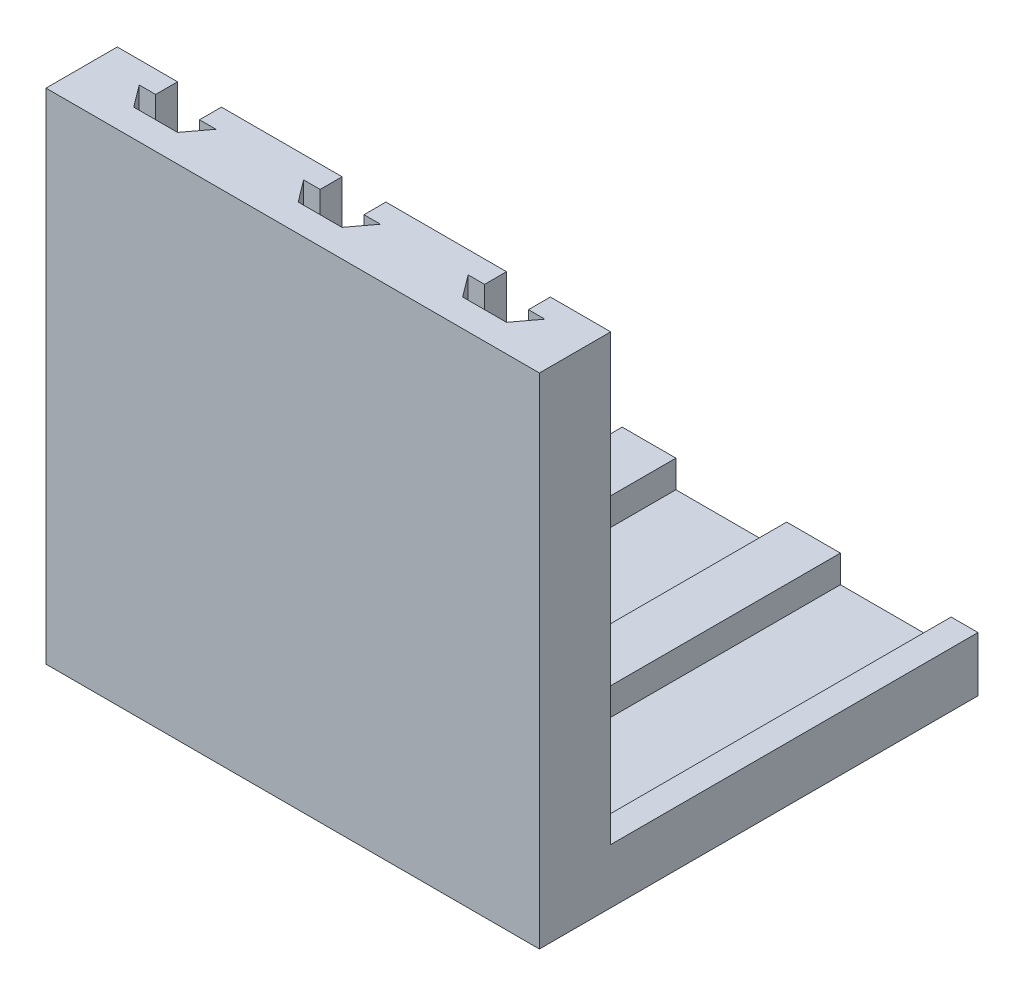
SolidWorks part; units mm, degrees
ref_plane "Front Plane" through (0, 0, 0) normal (0, 0, 1) x (1, 0, 0)
ref_plane "Top Plane" through (0, 0, 0) normal (0, 1, 0) x (1, 0, 0)
ref_plane "Right Plane" through (0, 0, 0) normal (1, 0, 0) x (0, 0, -1)
sketch "Sketch1" plane through (0, 0, 0) normal (0, 1, 0) x (1, 0, 0)
  line L1 (-15, -40) -> (15, -40)
  line L2 (-15, -40) -> (-15, 40)
  line L3 (-15, 40) -> (15, 40)
  line L4 (15, -40) -> (15, 40)
  line L5 (-15, -40) -> (15, 40) construction
  line L6 (-15, 40) -> (15, -40) construction
  point P0 (0, 0)
  dimension "D1" = 80
  dimension "D2" = 30
extrude "Boss-Extrude1" add sketch "Sketch1" along normal blind 10
sketch "Sketch2" plane through (0, 10, 0) normal (0, 1, 0) x (1, 0, 0)
  line L0 (15, -40) -> (15, 40) construction
  line L1 (-15, -40) -> (15, -40)
  line L2 (-15, -40) -> (-15, -27)
  line L3 (-15, -27) -> (15, -27)
  line L4 (15, -40) -> (15, -27)
  dimension "D1" = 13
extrude "Boss-Extrude2" add sketch "Sketch2" along normal blind 81 contours L3 L4 L1 L2
sketch "Sketch3" plane through (0, 91, 0) normal (0, 1, 0) x (1, 0, 0)
  line L0 (0, -27) -> (0, -40) construction
  line L1 (-15, -27) -> (15, -27) construction
  line L2 (-15, -40) -> (15, -40) construction
  line L3 (-4, -27) -> (4, -27)
  line L5 (-15, -27) -> (15, -27) construction
  line L6 (-4, -27) -> (-4, -31)
  line L7 (-4, -31) -> (-7, -31)
  line L8 (-7, -31) -> (-4, -35)
  line L9 (-4, -35) -> (4, -35)
  line L10 (4, -35) -> (7, -31)
  line L11 (7, -31) -> (4, -31)
  line L12 (4, -31) -> (4, -27)
  dimension "D1" = 8
  dimension "D2" = 4
  dimension "D3" = 4
  dimension "D4" = 3
extrude "Cut-Extrude1" cut sketch "Sketch3" against normal blind 40
sketch "Sketch4" plane through (0, 10, 0) normal (0, 1, 0) x (1, 0, 0)
  line L0 (0, 40) -> (0, -27) construction
  line L1 (15, 40) -> (-15, 40) construction
  line L2 (15, -27) -> (15, 40) construction
  line L3 (-15, -27) -> (15, -27) construction
  line L4 (-10.1, 40) -> (10.1, 40)
  line L5 (-10.1, 40) -> (-10.1, -27)
  line L7 (10.1, 40) -> (10.1, -27)
  line L8 (4, -27) -> (15, -27) construction
  line L10 (10.1, -27) -> (-10.1, -27)
  line L11 (-15, 40) -> (-15, -27) construction
  dimension "D1" = 20.2
  dimension "D2" = 4.9
extrude "Cut-Extrude2" cut sketch "Sketch4" against normal blind 5
sketch "Sketch5" plane through (0, 51, 0) normal (0, 1, 0) x (1, 0, 0)
  line L0 (0, -27) -> (0, -35) construction
  line L1 (4, -27) -> (-4, -27) construction
  line L2 (-4, -35) -> (4, -35) construction
  line L3 (4, -31) -> (4, -27) construction
  line L4 (-4, -27) -> (4, -27)
  line L5 (-4, -27) -> (-4, -29)
  line L6 (-4, -29) -> (4, -29)
  line L7 (4, -27) -> (4, -29)
  line L8 (-4, -27) -> (-4, -31) construction
  dimension "D1" = 2
extrude "Cut-Extrude3" cut sketch "Sketch5" against normal blind 46
pattern_linear "LPattern1" count 3 spacing 30 along (-1, 0, 0) of "Boss-Extrude1", "Boss-Extrude2", "Cut-Extrude1", "Cut-Extrude2", "Cut-Extrude3"
